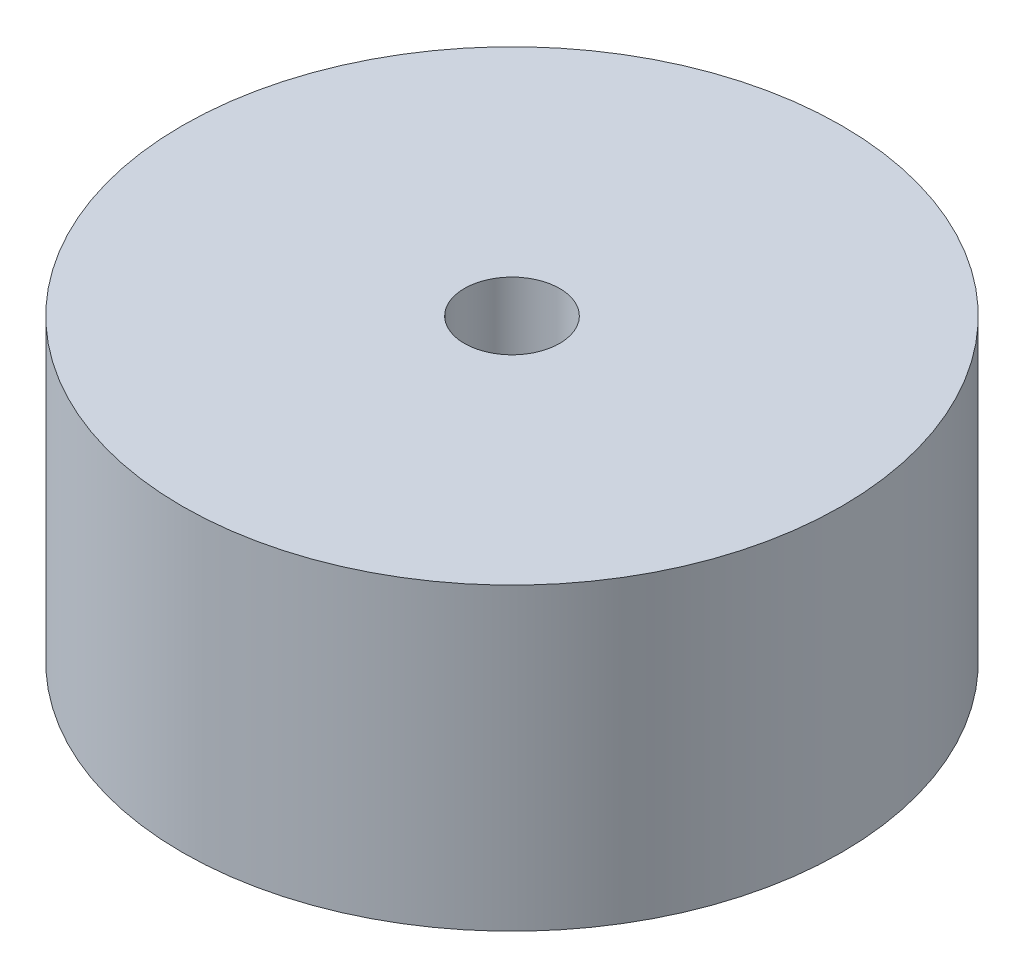
SolidWorks part; units mm, degrees
material "6061-T6 (SS)"
ref_plane "Front Plane" through (0, 0, 0) normal (0, 0, 1) x (1, 0, 0)
ref_plane "Top Plane" through (0, 0, 0) normal (0, 1, 0) x (1, 0, 0)
ref_plane "Right Plane" through (0, 0, 0) normal (1, 0, 0) x (0, 0, -1)
ref_axis "Axis1" through (0, 30.228, 0) along (0, -1, 0)
sketch "Sketch1" plane through (0, 0, 0) normal (0, 1, 0) x (1, 0, 0)
  circle A0 centre (0, 0) radius 12.7
  dimension "D1" = 25.4
curve "Helix/Spiral1" pitch 12.7 height 12.7 radius 12.7 centre (0, 0, 0) axis (0, 1, 0) start towards (0, 0, 1)
sketch "Sketch2" plane through (0, 0, 0) normal (0, 1, 0) x (1, 0, 0)
  line L1 (2.3812, 0) -> (-2.3812, 0)
  line L2 (2.3812, 0) -> (2.3813, -11.5888)
  line L4 (-2.3812, 0) -> (-2.3813, -11.5888)
  arc A0 (-2.3813, -11.5888) -> (2.3813, -11.5888) centre (0, -11.5888) ccw
  point P4 (0, -13.97)
  dimension "D1" = 13.97
  dimension "D2" = 4.7625
sweep "Sweep1" add profiles "Sketch2" path "Helix/Spiral1" parameters "D4"=0
sketch "Sketch4" plane through (0, 0, 0) normal (0, 0, 1) x (1, 0, 0)
  line L0 (0, 0) -> (0, 12.7)
  line L1 (0, 0) -> (6.35, 0)
  line L2 (6.35, 0) -> (2.947, 12.7)
  line L3 (0, 12.7) -> (-4.9832, 12.7) construction
  line L4 (0, 12.7) -> (2.947, 12.7)
  dimension "D1" = 6.35
  dimension "D2" = 12.7
  dimension "D3" = 15
revolve "Revolve1" add sketch "Sketch4" angle 360 about L0
pattern_circular "CirPattern1" count 4 over 360 about axis through (0, 30.228, 0) along (0, -1, 0) of "Sweep1"
hole_wizard "Tap Drill for #10-32 Tap1" positions "3DSketch1" profile "Sketch6" hole size "#10-32" standard "ANSI Inch" end condition through all
sketch3d "3DSketch1"
  arc A0 (-2.3802, 12.7, 1.7378) -> (-1.7378, 12.7, -2.3802) centre (0, 12.7, 0) ccw construction
  point P0 (0, 12.7, 0)
  point P6 (0, 9.753, 0)
sketch "Sketch6" plane through (0, 12.7, 0) normal (1, 0, 0) x (0, 0, 1)
  line L0 (0, 0) -> (0, 13.1836)
  line L1 (0, 13.1836) -> (2.0193, 13.1836)
  line L2 (2.0193, 13.1836) -> (2.0193, 0)
  line L5 (2.0193, 0) -> (0, 0)
  line L11 (0, -6.35) -> (0, 107.95) construction
  dimension "Thru Hole Dia." = 4.0386
  dimension "Thru Hole Depth" = 13.1836
sketch "Sketch7" plane through (0, 0, 0) normal (0, 0, 1) x (1, 0, 0)
  line L1 (2.0193, 12.7005) -> (13.97, 12.7005)
  line L2 (2.0193, 12.7005) -> (2.0193, 0)
  line L3 (2.0193, 0) -> (13.97, 0)
  line L4 (13.97, 12.7005) -> (13.97, 0)
revolve "Revolve2" add sketch "Sketch7" angle 360 about axis through (0, 30.228, 0) along (0, -1, 0)
